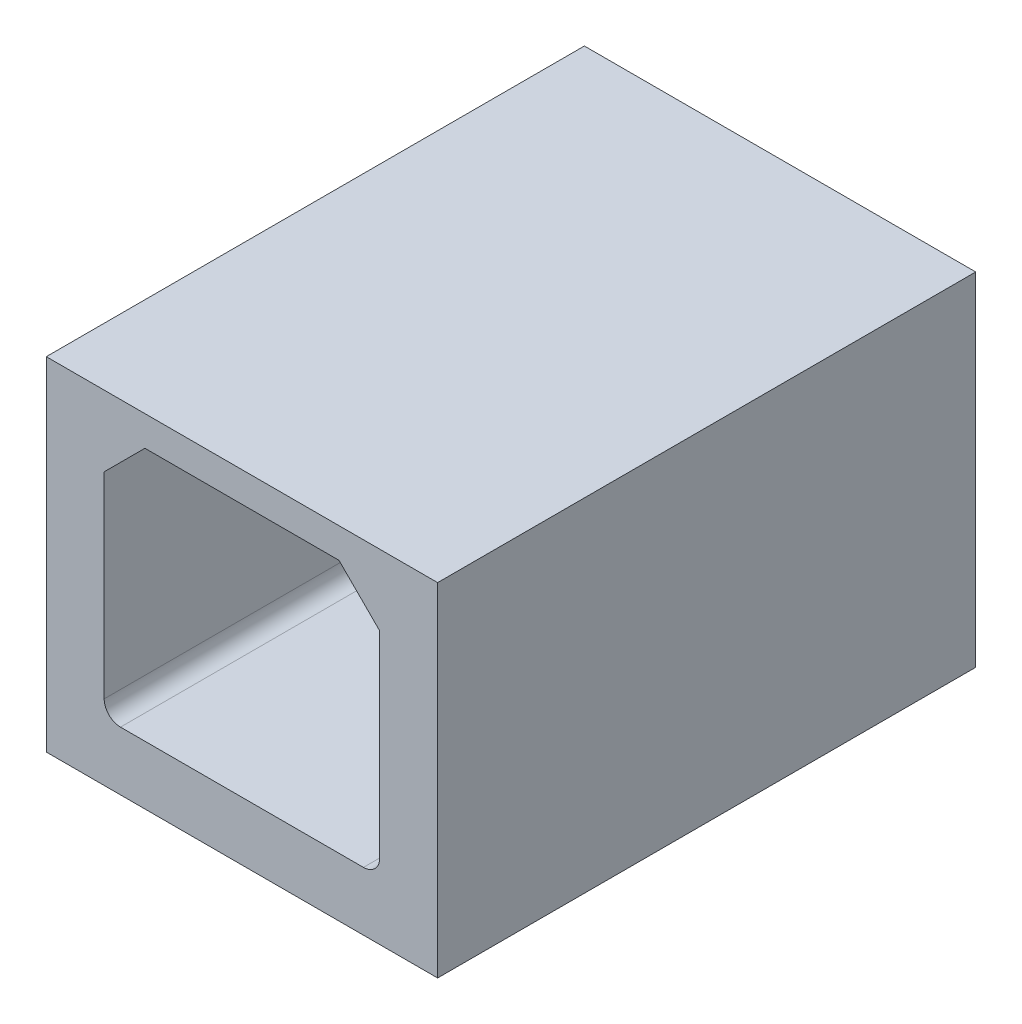
SolidWorks part; units mm, degrees
ref_plane "Front" through (0, 0, 0) normal (0, 0, 1) x (1, 0, 0)
ref_plane "Top" through (0, 0, 0) normal (0, 1, 0) x (1, 0, 0)
ref_plane "Right" through (0, 0, 0) normal (1, 0, 0) x (0, 0, -1)
sketch "Sketch1" plane through (0, 0, 0) normal (0, 0, 1) x (1, 0, 0)
  line L0 (-6, 5.25) -> (6, -5.25) construction
  line L1 (-6, 5.25) -> (6, 5.25)
  line L2 (-6, 5.25) -> (-6, -5.25)
  line L3 (-6, -5.25) -> (6, -5.25)
  line L4 (6, 5.25) -> (6, -5.25)
  dimension "D1" = 12
  dimension "D2" = 10.5
extrude "Base" add sketch "Sketch1" along normal mid plane 16.5
sketch "Sketch2" plane through (0, 0, 8.25) normal (0, 0, 1) x (1, 0, 0)
  line L0 (-2.975, 4.33) -> (-4.225, 3.08)
  line L1 (3.725, -3.45) -> (-3.725, -3.45)
  line L2 (4.225, -2.95) -> (4.225, 3.08)
  line L3 (2.975, 4.33) -> (-2.975, 4.33)
  line L4 (-4.225, -2.95) -> (-4.225, 3.08)
  line L5 (4.225, 3.08) -> (2.975, 4.33)
  line L6 (4.225, 4.33) -> (-4.225, -3.45) construction
  line L7 (6, 5.25) -> (-6, 5.25) construction
  line L9 (0, 0.44) -> (13.9883, 0.44) construction
  arc A0 (-3.725, -3.45) -> (-4.225, -2.95) centre (-3.725, -2.95) cw
  arc A1 (3.725, -3.45) -> (4.225, -2.95) centre (3.725, -2.95) ccw
  point P1 (4.225, 4.33)
  point P2 (-4.225, 4.33)
  point P12 (-4.225, -3.45)
  dimension "D1" = 0.5
  dimension "D2" = 4.81
  dimension "D3" = 8.45
  dimension "D5" = 7.78
extrude "Contact Opening" cut sketch "Sketch2" against normal blind 9
